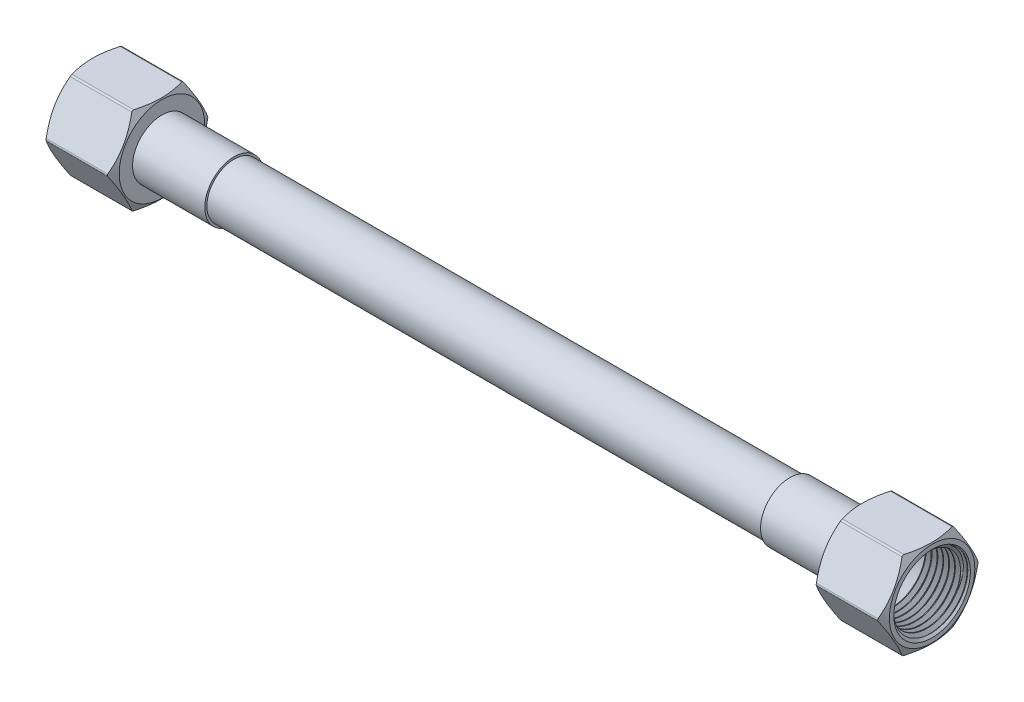
SolidWorks part; units mm, degrees
ref_plane "Front Plane" through (0, 0, 0) normal (0, 0, 1) x (1, 0, 0)
ref_plane "Top Plane" through (0, 0, 0) normal (0, 1, 0) x (1, 0, 0)
ref_plane "Right Plane" through (0, 0, 0) normal (1, 0, 0) x (0, 0, -1)
sketch "Sketch1" plane through (0, 0, 0) normal (0, 0, 1) x (1, 0, 0)
  line L0 (152.4, 0) -> (-152.4, 0) construction
  line L1 (-127, -13.4938) -> (-127, 13.4937) construction
  line L2 (-127, 13.4937) -> (-152.4, 13.4937) construction
  line L3 (0, 9.8806) -> (0, -9.8806) construction
  line L4 (-152.4, 13.4937) -> (-152.4, 0) construction
  line L5 (-127, 13.4937) -> (-129.1167, 13.4937) construction
  line L6 (-152.4, 15.875) -> (-127, 15.875) construction
  line L7 (-127, 10.6426) -> (-100.8063, 10.6426) construction
  line L10 (-127, 0) -> (-144.9068, 13.4937) construction
  line L11 (-152.4, -13.4938) -> (-152.4, 13.4937) construction
  line L12 (152.4, 13.4937) -> (152.4, 0) construction
  line L13 (152.4, -13.4937) -> (152.4, 13.4937) construction
  point P3 (-73.8188, 0)
  point P4 (0, 0)
  point P8 (-127, 0)
  point P11 (0, 7.9375)
  point P20 (73.8188, 0)
  point P30 (-137.3188, 13.4937)
  point P40 (-152.4, -13.4938)
  point P42 (-152.4, 0)
  point P45 (152.4, 0)
  point P46 (152.4, -13.4937)
  point P47 (-94.0594, -9.8806)
  dimension "Thread Size" = 26.9875
  dimension "OD" = 19.7612
  dimension "ID" = 15.875
  dimension "Pitch" = 2.1167
  dimension "Hex Length" = 25.4
  dimension "Hex Width" = 31.75
  dimension "Length" = 304.8
  dimension "D5" = 26.1937
  dimension "D2" = 0.762
  dimension "D1" = 26.9875
  dimension "Flared Angle" = 37
  dimension "Thread Length" = 15.0812
  dimension "D3" = 6.7469
sketch "Sketch2" plane through (0, 0, 0) normal (1, 0, 0) x (0, 0, -1)
  line L0 (-8.7072, -15.0812) -> (0, 0) construction
  line L1 (8.7072, 15.875) -> (-8.7072, 15.875)
  line L2 (-9.3946, 15.4781) -> (-18.1017, 0.3969)
  line L3 (-18.1017, -0.3969) -> (-9.3946, -15.4781)
  line L4 (-8.7072, -15.875) -> (8.7072, -15.875)
  line L5 (9.3946, -15.4781) -> (18.1017, -0.3969)
  line L6 (18.1017, 0.3969) -> (9.3946, 15.4781)
  circle A0 centre (0, 0) radius 15.875 construction
  arc A1 (8.7072, -15.875) -> (9.3946, -15.4781) centre (8.7072, -15.0812) ccw
  circle A2 centre (0, 0) radius 13.4937
  arc A3 (18.1017, -0.3969) -> (18.1017, 0.3969) centre (17.4143, 0) ccw
  arc A4 (-9.3946, -15.4781) -> (-8.7072, -15.875) centre (-8.7072, -15.0812) ccw
  arc A5 (-18.1017, 0.3969) -> (-18.1017, -0.3969) centre (-17.4143, 0) ccw
  arc A6 (-8.7072, 15.875) -> (-9.3946, 15.4781) centre (-8.7072, 15.0812) ccw
  arc A7 (8.7072, 15.875) -> (9.3946, 15.4781) centre (8.7072, 15.0812) cw
  point P9 (-6.7469, -11.6859)
  dimension "D1" = 0.7937
extrude "Boss-Extrude1" add sketch "Sketch2" along normal up to vertex (-127 mm away) from vertex up to point (-127, 15.875, 0) starting at point (-152.4, 15.875, 0)
sketch "Sketch3" plane through (-152.4, 0, 0) normal (-1, 0, 0) x (0, 0, 1)
  circle A1 centre (0, 0) radius 15.494
  dimension "D1" = 0.381
extrude "Cut-Extrude1" cut sketch "Sketch3" against normal through all draft 60 flip side to cut
extrude "Cut-Extrude2" cut sketch "Sketch4<2>" along normal through all draft 60 from surface flip side to cut starting at face at (-127, 0, 0)
sketch "Sketch4<2>" plane through (-152.4, 0, 0) normal (-1, 0, 0) x (0, 0, 1) same geometry as "Sketch3"
sketch "Sketch4" plane through (-127, 0, 0) normal (1, 0, 0) x (0, 0, -1)
  line L0 (0, 9.8806) -> (0, -9.8806) construction
  line L1 (0, 9.8806) -> (0, -9.8806) construction
  circle A0 centre (0, 0) radius 13.4937 construction
  circle A1 centre (0, 0) radius 13.4937
  circle A2 centre (0, 0) radius 10.6426
  point P7 (0, 7.9375)
extrude "Boss-Extrude2" add sketch "Sketch4" against normal blind 1.5875
sketch "Sketch5" plane through (0, 0, 0) normal (0, 0, 1) x (1, 0, 0)
  line L7 (-100.8063, 10.6426) -> (-128.5875, 10.6426)
  line L16 (-127, -13.4938) -> (-127, 13.4937) construction
  line L17 (-127, 0) -> (-144.9068, 13.4937) construction
  line L32 (-128.5875, 10.6426) -> (-128.5875, 13.4937)
  line L33 (-127, 13.4937) -> (-152.4, 13.4937) construction
  line L34 (-128.5875, 13.4937) -> (-137.3188, 13.4937)
  line L35 (-137.3188, 13.4937) -> (-137.3188, 13.3667)
  line L36 (-137.3188, 13.3667) -> (-130.1139, 7.9375)
  line L37 (-130.1139, 7.9375) -> (-127, 7.9375)
  line L38 (-127, 7.9375) -> (-127, 9.8806)
  line L39 (-127, 9.8806) -> (-100.8063, 9.8806)
  line L40 (-100.8063, 9.8806) -> (-100.8063, 10.6426)
  line L41 (152.4, 0) -> (-152.4, 0) construction
  line L42 (152.4, 0) -> (-152.4, 0) construction
  line L46 (-128.5875, 13.4937) -> (-128.5875, -13.4937) construction
  dimension "D1" = 0.127
  dimension "D3" = 15.0812
revolve "Revolve1" add sketch "Sketch5" angle 360 about L0
mirror "Mirror1" about plane through (0, 0, 0) normal (1, 0, 0) of bodies 144 143
sketch "Sketch6" plane through (-127, 0, 0) normal (1, 0, 0) x (0, 0, -1)
  circle A5 centre (0, 0) radius 9.8806
  circle A6 centre (0, 0) radius 7.9375
extrude "Boss-Extrude3" add sketch "Sketch6" along normal up to surface (254 mm away) separate body up to face at (127, 9.8806, 0)
sketch "Sketch7" plane through (-152.4, 0, 0) normal (-1, 0, 0) x (0, 0, 1)
  circle A0 centre (0, 0) radius 13.4937 construction
  circle A1 centre (0, 0) radius 13.4937
extrude "Boss-Extrude4" add sketch "Sketch7" against normal up to surface (15.0813 mm away) separate body up to face at (-137.3188, 13.3667, 0)
extrude "Boss-Extrude5" add sketch "Sketch8<2>" against normal up to surface (15.0813 mm away) up to face at (-137.3188, 13.3667, 0)
sketch "Sketch8<2>" plane through (-152.4, 0, 0) normal (-1, 0, 0) x (0, 0, 1) same geometry as "Sketch7"
sketch "Sketch8" plane through (-152.4, 0, 0) normal (-1, 0, 0) x (0, 0, 1)
  circle A0 centre (0, 0) radius 13.4937 construction
  circle A1 centre (0, 0) radius 13.4937
curve "Helix/Spiral1" pitch 2.1167 height 17.1979 radius 13.4937 centre (-152.4, 0, 0) axis (1, 0, 0) start towards (0, 1, 0)
sketch "Sketch9" plane through (0, 0, 0) normal (0, 0, 1) x (1, 0, 0)
  line L0 (-154.3844, 13.7229) -> (-153.326, 11.8898) construction
  line L1 (-153.326, 11.8898) -> (-152.2677, 13.7229) construction
  line L2 (-152.2677, 13.7229) -> (-154.3844, 13.7229) construction
  line L3 (-154.2521, 13.4937) -> (-152.4, 13.4937) construction
  line L4 (-153.326, 13.7229) -> (-153.326, 13.4937) construction
  line L5 (-153.326, 13.4937) -> (-153.326, 12.1189) construction
  line L6 (-153.326, 12.1189) -> (-153.326, 11.8898) construction
  line L7 (-153.4583, 12.1189) -> (-153.1937, 12.1189)
  line L8 (-154.3182, 13.6083) -> (-152.3339, 13.6083)
  line L9 (-153.1937, 12.1189) -> (-152.3339, 13.6083)
  line L10 (-153.4583, 12.1189) -> (-154.3182, 13.6083)
  point P12 (-153.326, 13.6083)
  dimension "D1" = 2.1167
  dimension "D2" = 0.2646
sweep "Cut-Sweep1" cut profiles "Sketch9" path "Helix/Spiral1" align with end faces yes
combine bodies "Combine1" operation type subtract main body 149 bodies to subtract 150
sketch "Sketch10" plane through (-152.4, 0, 0) normal (-1, 0, 0) x (0, 0, 1)
  circle A0 centre (0, 0) radius 13.4937 construction
  circle A1 centre (0, 0) radius 13.4937 construction
  circle A2 centre (0, 0) radius 13.8906
  dimension "D1" = 0.3969
extrude "Cut-Extrude3" cut sketch "Sketch10" against normal through all draft 45
delete or keep bodies "Body-Delete/Keep 1" type delete bodies bodies 146
pattern_circular "CirPattern1" count 2 over 360 about axis through (0, 9.8806, 0) along (0, -1, 0) of bodies 152
equation "\"D4@Helix/Spiral1\"=\"Pitch@Sketch1\""
equation "\"D3@Helix/Spiral1\"=\"D3@Sketch5\"+\"Pitch@Sketch1\""
equation "\"D2@Sketch9\" = \"D1@Sketch9\" / 8"
equation "\"D1@Sketch9\" = \"Pitch@Sketch1\""
equation "\"D5@Sketch1\" = \"Hex Length@Sketch1\" + .03125"
equation "\"D1@Sketch1\"=\"Thread Size@Sketch1\""
equation "\"Thread Length@Sketch1\"=\"Hex Length@Sketch1\" * .59375"
equation "\"D3@Sketch1\"=\"D1@Sketch1\"/4"
